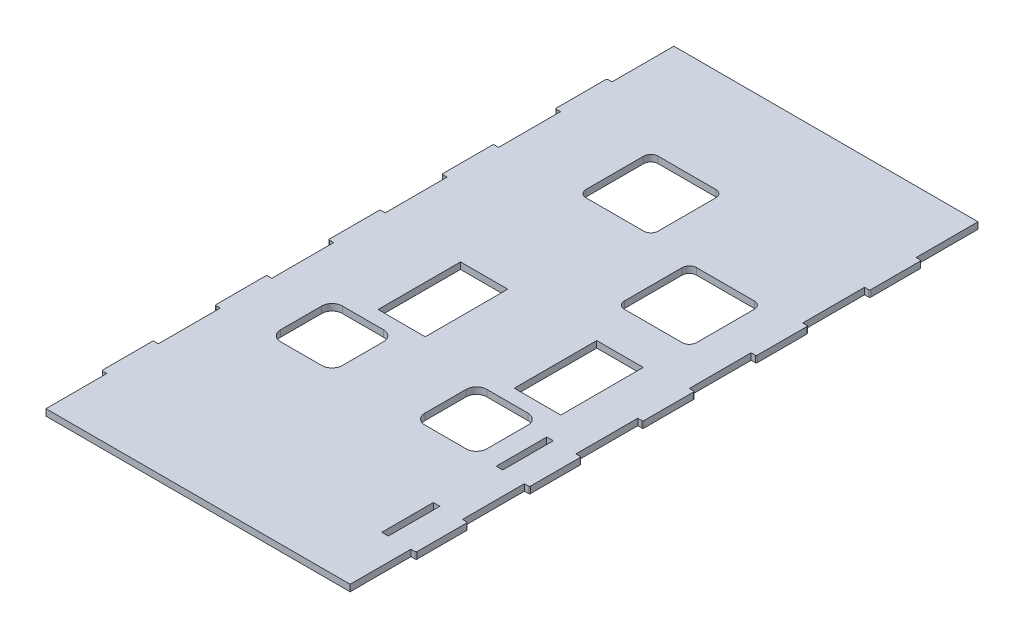
SolidWorks part; units mm, degrees
material "Oak"
ref_plane "Front Plane" through (0, 0, 0) normal (0, 0, 1) x (1, 0, 0)
ref_plane "Top Plane" through (0, 0, 0) normal (0, 1, 0) x (1, 0, 0)
ref_plane "Right Plane" through (0, 0, 0) normal (1, 0, 0) x (0, 0, -1)
sketch "Sketch1" plane through (0, 0, 0) normal (0, 1, 0) x (1, 0, 0)
  line L0 (157.0736, 348.6213) -> (157.0736, 288.6213)
  line L1 (-137.9264, 348.6213) -> (157.0736, 348.6213)
  line L3 (-137.9264, -260.3787) -> (157.0859, -260.3787)
  line L9 (157.0736, 288.6213) -> (162.0736, 288.6213)
  line L10 (162.0736, 288.6213) -> (162.0859, 238.6213)
  line L11 (162.0859, 238.6213) -> (157.0859, 238.6213)
  line L12 (157.0859, 238.6213) -> (157.0859, 178.6213)
  line L13 (157.0859, 178.6213) -> (162.0859, 178.6213)
  line L14 (162.0859, 178.6213) -> (162.0859, 128.6213)
  line L15 (162.0859, 128.6213) -> (157.0859, 128.6213)
  line L16 (157.0859, 128.6213) -> (157.0859, 68.6213)
  line L17 (157.0859, 68.6213) -> (162.0859, 68.6213)
  line L18 (162.0859, 68.6213) -> (162.0859, 18.6213)
  line L19 (162.0859, 18.6213) -> (157.0859, 18.6213)
  line L20 (157.0859, 18.6213) -> (157.0859, -41.3787)
  line L21 (157.0859, -41.3787) -> (162.0859, -41.3787)
  line L22 (162.0859, -41.3787) -> (162.0859, -91.3787)
  line L23 (162.0859, -91.3787) -> (157.0859, -91.3787)
  line L24 (157.0859, -91.3787) -> (157.0859, -151.3787)
  line L25 (157.0859, -151.3787) -> (162.0859, -151.3787)
  line L26 (162.0859, -151.3787) -> (162.0859, -201.3787)
  line L27 (162.0859, -201.3787) -> (157.0859, -201.3787)
  line L28 (157.0859, -201.3787) -> (157.0859, -260.3787)
  line L29 (-137.9264, 348.6213) -> (-137.9264, 288.6213)
  line L30 (-137.9264, 288.6213) -> (-142.9387, 288.6213)
  line L31 (-142.9387, 288.6213) -> (-142.9387, 238.6213)
  line L32 (-142.9387, 238.6213) -> (-137.9264, 238.6213)
  line L33 (-137.9264, 238.6213) -> (-137.9264, 178.6213)
  line L34 (-137.9264, 178.6213) -> (-142.9387, 178.6213)
  line L35 (-142.9387, 178.6213) -> (-142.9387, 128.6213)
  line L36 (-142.9387, 128.6213) -> (-137.9264, 128.6213)
  line L37 (-137.9264, 128.6213) -> (-137.9264, 68.6213)
  line L38 (-137.9264, 68.6213) -> (-142.9387, 68.6213)
  line L39 (-142.9387, 68.6213) -> (-142.9387, 18.6213)
  line L40 (-142.9387, 18.6213) -> (-137.9264, 18.6213)
  line L41 (-137.9264, 18.6213) -> (-137.9264, -41.3787)
  line L42 (-137.9264, -41.3787) -> (-142.9264, -41.3787)
  line L43 (-142.9264, -41.3787) -> (-142.9264, -91.3787)
  line L44 (-142.9264, -91.3787) -> (-137.9264, -91.3787)
  line L45 (-137.9264, -91.3787) -> (-137.9264, -151.3787)
  line L46 (-137.9264, -151.3787) -> (-142.9387, -151.3787)
  line L47 (-142.9387, -151.3787) -> (-142.9387, -201.3787)
  line L48 (-142.9387, -201.3787) -> (-137.9264, -201.3787)
  line L49 (-137.9264, -201.3787) -> (-137.9264, -260.3787)
  line L50 (128.7359, -259.5286) -> (128.7359, -159.5286) construction
  line L51 (128.7359, -159.5286) -> (-137.9141, -110.3787) construction
  line L52 (-137.9141, -110.3787) -> (-137.9141, -60.3787) construction
  line L53 (-137.9141, -60.3787) -> (162.0859, -60.3787) construction
  line L55 (-80.4688, -30.3787) -> (-40.4688, -30.3787)
  line L56 (-90.4688, -40.3787) -> (-90.4688, -80.3787)
  line L57 (-80.4688, -90.3787) -> (-40.4688, -90.3787)
  line L58 (-30.4688, -40.3787) -> (-30.4688, -80.3787)
  line L59 (-90.4688, -30.3787) -> (-30.4688, -90.3787) construction
  line L60 (-90.4688, -90.3787) -> (-30.4688, -30.3787) construction
  line L61 (59.5859, -30.3787) -> (99.5859, -30.3787)
  line L62 (49.5859, -40.3787) -> (49.5859, -80.3787)
  line L63 (59.5859, -90.3787) -> (99.5859, -90.3787)
  line L64 (109.5859, -40.3787) -> (109.5859, -80.3787)
  line L65 (49.5859, -30.3787) -> (109.5859, -90.3787) construction
  line L66 (49.5859, -90.3787) -> (109.5859, -30.3787) construction
  line L67 (128.7359, -201.3787) -> (135.0859, -201.3787)
  line L68 (128.7359, -201.3787) -> (128.7359, -151.3787)
  line L69 (128.7359, -151.3787) -> (135.0859, -151.3787)
  line L70 (135.0859, -201.3787) -> (135.0859, -151.3787)
  line L71 (128.7359, -90.3787) -> (135.0859, -90.3787)
  line L72 (128.7359, -90.3787) -> (128.7359, -41.3787)
  line L73 (128.7359, -41.3787) -> (135.0859, -41.3787)
  line L74 (135.0859, -90.3787) -> (135.0859, -41.3787)
  line L75 (-53.198, 248.6213) -> (2.802, 248.6213)
  line L76 (-60.198, 241.6213) -> (-60.198, 185.6213)
  line L77 (-53.198, 178.6213) -> (2.802, 178.6213)
  line L78 (9.802, 241.6213) -> (9.802, 185.6213)
  line L83 (59.0859, 173.6213) -> (115.0859, 173.6213)
  line L84 (52.0859, 166.6213) -> (52.0859, 110.6213)
  line L85 (59.0859, 103.6213) -> (115.0859, 103.6213)
  line L86 (122.0859, 166.6213) -> (122.0859, 110.6213)
  line L87 (-60.198, 63.9367) -> (-14.3725, 63.9367)
  line L88 (-60.198, 63.9367) -> (-60.198, -16.0633)
  line L89 (-60.198, -16.0633) -> (-14.3725, -16.0633)
  line L90 (-14.3725, 63.9367) -> (-14.3725, -16.0633)
  line L91 (71.9462, 63.9367) -> (117.0859, 63.9367)
  line L92 (71.9462, 63.9367) -> (71.9462, -16.0633)
  line L93 (71.9462, -16.0633) -> (117.0859, -16.0633)
  line L94 (117.0859, 63.9367) -> (117.0859, -16.0633)
  arc A0 (99.5859, -30.3787) -> (109.5859, -40.3787) centre (99.5859, -40.3787) cw
  arc A1 (109.5859, -80.3787) -> (99.5859, -90.3787) centre (99.5859, -80.3787) cw
  arc A2 (59.5859, -90.3787) -> (49.5859, -80.3787) centre (59.5859, -80.3787) cw
  arc A3 (49.5859, -40.3787) -> (59.5859, -30.3787) centre (59.5859, -40.3787) cw
  arc A4 (-90.4688, -80.3787) -> (-80.4688, -90.3787) centre (-80.4688, -80.3787) ccw
  arc A5 (-40.4688, -90.3787) -> (-30.4688, -80.3787) centre (-40.4688, -80.3787) ccw
  arc A6 (-40.4688, -30.3787) -> (-30.4688, -40.3787) centre (-40.4688, -40.3787) cw
  arc A7 (-80.4688, -30.3787) -> (-90.4688, -40.3787) centre (-80.4688, -40.3787) ccw
  arc A12 (2.802, 248.6213) -> (9.802, 241.6213) centre (2.802, 241.6213) cw
  arc A13 (9.802, 185.6213) -> (2.802, 178.6213) centre (2.802, 185.6213) cw
  arc A14 (-53.198, 178.6213) -> (-60.198, 185.6213) centre (-53.198, 185.6213) cw
  arc A15 (-60.198, 241.6213) -> (-53.198, 248.6213) centre (-53.198, 241.6213) cw
  arc A16 (115.0859, 173.6213) -> (122.0859, 166.6213) centre (115.0859, 166.6213) cw
  arc A17 (122.0859, 110.6213) -> (115.0859, 103.6213) centre (115.0859, 110.6213) cw
  arc A18 (59.0859, 103.6213) -> (52.0859, 110.6213) centre (59.0859, 110.6213) cw
  arc A19 (52.0859, 166.6213) -> (59.0859, 173.6213) centre (59.0859, 166.6213) cw
  point P46 (-90.4141, -60.3787)
  point P54 (61.387, -60.3787)
  point P97 (122.0859, 173.6213)
  point P107 (52.0859, 103.6213)
  point P110 (52.0859, 173.6213)
  point P114 (9.802, 248.6213)
  point P119 (-60.198, 178.6213)
  point P122 (-60.198, 248.6213)
  dimension "D29" = 10
  dimension "D38" = 175
  dimension "D37" = 7
  dimension "D1" = 295
  dimension "D2" = 609
  dimension "D3" = 60
  dimension "D4" = 5
  dimension "D5" = 50
  dimension "D6" = 60
  dimension "D7" = 50
  dimension "D8" = 60
  dimension "D9" = 50
  dimension "D10" = 60
  dimension "D11" = 50
  dimension "D12" = 60
  dimension "D13" = 59
  dimension "D14" = 50
  dimension "D15" = 5
  dimension "D16" = 5
  dimension "D17" = 28.35
  dimension "D18" = 100
  dimension "D19" = 150
  dimension "D20" = 50
  dimension "D21" = 47.5
  dimension "D22" = 60
  dimension "D23" = 60
  dimension "D24" = 30
  dimension "D25" = 60
  dimension "D26" = 60
  dimension "D27" = 30
  dimension "D28" = 47.5
  dimension "D30" = 6.35
  dimension "D31" = 6.35
  dimension "D32" = 70
  dimension "D33" = 70
  dimension "D34" = 70
  dimension "D35" = 70
  dimension "D36" = 100
  dimension "D39" = 80
  dimension "D40" = 80
  dimension "D41" = 40
  dimension "D42" = 35
extrude "Boss-Extrude1" add sketch "Sketch1" along normal blind 6.35
fillet "Fillet1" radius 1 20 edges at (-142.9387, 3.175, -288.6213) (-142.9387, 3.175, -238.6213) (-142.9387, 3.175, -178.6213) (-142.9387, 3.175, -128.6213) (-142.9387, 3.175, -68.6213) (-142.9387, 3.175, -18.6213) (-142.9264, 3.175, 41.3787) (-142.9264, 3.175, 91.3787) (-140.4325, 0, 151.3787) (-142.9387, 3.175, 201.3787) (162.0736, 3.175, -288.6213) (162.0859, 3.175, -238.6213) (162.0859, 3.175, -178.6213) (162.0859, 3.175, -128.6213) (162.0859, 3.175, -68.6213) (162.0859, 3.175, -18.6213) (162.0859, 3.175, 41.3787) (162.0859, 3.175, 91.3787) (162.0859, 3.175, 151.3787) (162.0859, 3.175, 201.3787)
